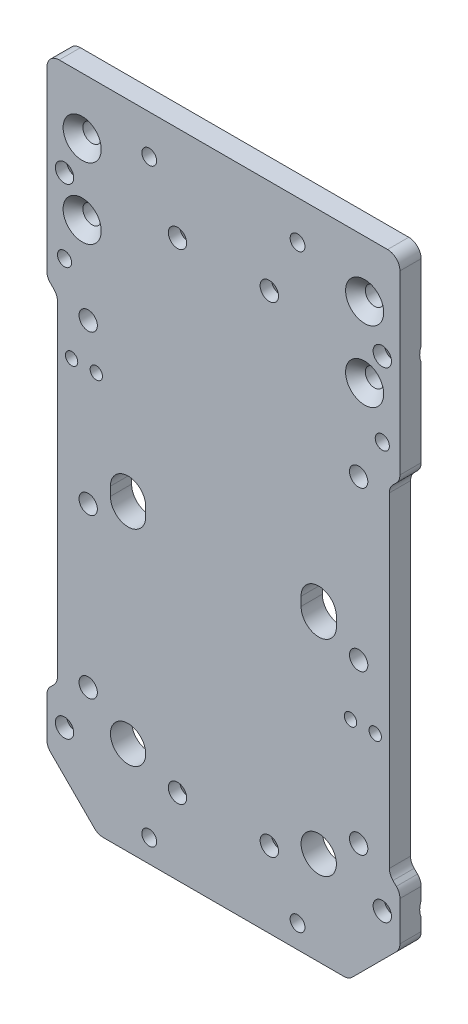
SolidWorks part; units mm, degrees
material "Acrylic (Medium-high impact)"
ref_plane "Front Plane" through (0, 0, 0) normal (0, 0, 1) x (1, 0, 0)
ref_plane "Top Plane" through (0, 0, 0) normal (0, 1, 0) x (1, 0, 0)
ref_plane "Right Plane" through (0, 0, 0) normal (1, 0, 0) x (0, 0, -1)
sketch "Sketch1" plane through (0, 0, 0) normal (0, 0, 1) x (1, 0, 0)
  line L0 (-50, 0) -> (-35.5, -14.5)
  line L1 (-50, 0) -> (50, 0)
  line L2 (-50, 0) -> (-50, 170)
  line L3 (-50, 170) -> (50, 170)
  line L4 (50, 0) -> (50, 170)
  line L5 (-35.5, -14.5) -> (35.5, -14.5)
  line L6 (35.5, -14.5) -> (50, 0)
  point P4 (0, 0)
  point P8 (0, -14.5)
  dimension "D1" = 100
  dimension "D2" = 170
  dimension "D3" = 14.5
  dimension "D4" = 45
extrude "Body" add sketch "Sketch1" along normal mid plane 6 contours L1 L4 L3 L2 | L5 L6 L1 L0 region at (0, -6.8402, 0) region at (0, 85, 0)
sketch "Sketch2" plane through (0, 0, 3) normal (0, 0, 1) x (1, 0, 0)
  line L0 (0, 0) -> (0, 32.3546) construction
  circle A0 centre (-38.3, 20.2) radius 2.6
  circle A1 centre (38.3, 20.2) radius 2.6
  circle A2 centre (-38.3, 110.2) radius 2.6
  circle A3 centre (38.3, 110.2) radius 2.6
  circle A4 centre (-38.3, 65.2) radius 2.6
  circle A5 centre (38.3, 65.2) radius 2.6
  dimension "D1" = 76.6
  dimension "D2" = 5.2
  dimension "D3" = 20.2
  dimension "D4" = 90
  dimension "D5" = 45
extrude "MountToBaseHoles" cut sketch "Sketch2" against normal through all
sketch "Sketch3" plane through (0, 0, 3) normal (0, 0, 1) x (1, 0, 0)
  line L0 (-13, 7) -> (-45, 7) construction
  line L1 (-38.3, 110.2) -> (-77.9825, 110.2) construction
  line L2 (13, 7) -> (13, 37.5378) construction
  line L4 (-13, 7) -> (-13, 44.3761) construction
  line L5 (0, 0) -> (0, 40.72) construction
  circle A0 centre (-45, 7) radius 2.6
  circle A1 centre (-45, 143.1) radius 2.6
  circle A2 centre (45, 143.1) radius 2.6
  circle A3 centre (45, 7) radius 2.6
  circle A6 centre (-13, 143.1) radius 2.6
  circle A7 centre (13, 143.1) radius 2.6
  circle A8 centre (-13, 7) radius 2.6
  circle A9 centre (13, 7) radius 2.6
  dimension "D1" = 5.2
  dimension "D4" = 136.1
  dimension "D6" = 32
  dimension "D2" = 32
  dimension "D3" = 26
  dimension "D7" = 13
  dimension "D5" = 7
extrude "MountRodHoles" cut sketch "Sketch3" against normal through all
sketch "Sketch4" plane through (0, 0, -3) normal (0, 0, -1) x (-1, 0, 0)
  line L1 (0, 0) -> (0, 34.6557) construction
  line L2 (50, 170) -> (-50, 170) construction
  circle A0 centre (-40, 154) radius 2.6
  circle A2 centre (40, 154) radius 2.6
  circle A4 centre (40, 134) radius 2.6
  circle A6 centre (-40, 134) radius 2.6
  dimension "D4" = 5.2
  dimension "D1" = 16
  dimension "D2" = 40
  dimension "D5" = 20
extrude "MountAngleCornerHoles" cut sketch "Sketch4" against normal through all
sketch "Sketch5" plane through (0, 0, -3) normal (0, 0, -1) x (-1, 0, 0)
  circle A0 centre (-21, -8) radius 2.1
  circle A1 centre (21, -8) radius 2.1
  circle A2 centre (-21, 159) radius 2.1
  circle A3 centre (21, 159) radius 2.1
  dimension "D5" = 4.2
  dimension "D1" = 42
  dimension "D2" = 21
  dimension "D3" = 167
  dimension "D4" = 8
extrude "KP8_Holes" cut sketch "Sketch5" against normal through all
chamfer "ChamferForSlottedFlatHeadScrews" distance 2.8 angle 45 14 edges at (-23.1, -8, -3) (-10.4, 7, -3) (15.6, 7, -3) (18.9, -8, -3) (-42.4, 143.1, -3) (-10.4, 143.1, -3) (15.6, 143.1, -3) (47.6, 143.1, -3) (-42.4, 7, -3) (47.6, 7, -3) (-42.6, 154, 3) (-42.6, 134, 3) (37.4, 154, 3) (37.4, 134, 3)
sketch "Sketch6" plane through (0, 0, 3) normal (0, 0, 1) x (1, 0, 0)
  line L0 (-50, 115) -> (-47, 112)
  line L1 (0, 0) -> (0, 25.1631) construction
  line L2 (-47, 112) -> (-47, 17)
  line L3 (-47, 17) -> (-50, 14)
  line L4 (50, 115) -> (47, 112)
  line L6 (47, 112) -> (47, 17)
  line L7 (47, 17) -> (50, 14)
  line L8 (-50, 115) -> (-50, 14)
  line L9 (50, 115) -> (50, 14)
  line L12 (-50, 0) -> (-50, 170) construction
  line L13 (50, 0) -> (50, 170) construction
  dimension "D1" = 3
  dimension "D2" = 3
  dimension "D3" = 45
  dimension "D5" = 115
  dimension "D4" = 14
extrude "ReduceSomeWidth" cut sketch "Sketch6" against normal through all
sketch "screwHeadHoleCarriageY" plane through (0, 0, -3) normal (0, 0, -1) x (-1, 0, 0)
  line L0 (0, 0) -> (0, 34.2129) construction
  line L2 (-27, 70.2) -> (-27, 72.7) construction
  line L3 (-32, 70.2) -> (-32, 72.7)
  line L4 (-22, 70.2) -> (-22, 72.7)
  line L5 (27, 70.2) -> (27, 72.7) construction
  line L6 (22, 70.2) -> (22, 72.7)
  line L7 (32, 70.2) -> (32, 72.7)
  circle A0 centre (-27, 12) radius 5
  circle A1 centre (27, 12) radius 5
  arc A6 (-32, 70.2) -> (-22, 70.2) centre (-27, 70.2) ccw
  arc A7 (-22, 72.7) -> (-32, 72.7) centre (-27, 72.7) ccw
  arc A8 (22, 70.2) -> (32, 70.2) centre (27, 70.2) ccw
  arc A9 (32, 72.7) -> (22, 72.7) centre (27, 72.7) ccw
  point P18 (-27, 71.45)
  point P28 (27, 71.45)
  dimension "D3" = 10
  dimension "D5" = 12.5
  dimension "D1" = 54
  dimension "D2" = 12
  dimension "D4" = 59.45
extrude "CutForOherScrewsHeads" cut sketch "screwHeadHoleCarriageY" against normal through all
sketch "Sketch7" plane through (0, 0, 3) normal (0, 0, 1) x (1, 0, 0)
  line L0 (-35.5, -14.5) -> (35.5, -14.5) construction
  line L2 (50, 0) -> (50, 14) construction
  line L3 (-50, 0) -> (-50, 14) construction
  circle A0 centre (43, 49.5) radius 1.75
  circle A1 centre (36, 49.5) radius 1.75
  circle A2 centre (-36, 98.5) radius 1.75
  circle A3 centre (-43, 98.5) radius 1.75
  dimension "D3" = 3.5
  dimension "D1" = 64
  dimension "D2" = 7
  dimension "D4" = 7
  dimension "D5" = 7
  dimension "D6" = 7
  dimension "D7" = 113
extrude "EndSensorsHoles" cut sketch "Sketch7" against normal through all
chamfer "ChamferEndSensors" distance 1.5 angle 45 4 edges at (37.75, 49.5, -3) (44.75, 49.5, -3) (-41.25, 98.5, -3) (-34.25, 98.5, -3)
sketch "Sketch8" plane through (0, 0, 3) normal (0, 0, 1) x (1, 0, 0)
  line L0 (0, 0) -> (0, 36.091) construction
  circle A0 centre (45, 122) radius 2
  circle A1 centre (-45, 122) radius 2
  dimension "D1" = 4
  dimension "D2" = 90
  dimension "D3" = 122
extrude "CableTieHoles" cut sketch "Sketch8" against normal through all
fillet "EndMillMinimumRadius" radius 3.5 14 edges at (-50, 170, 0) (50, 170, 0) (47, 112, 0) (47, 17, 0) (-47, 17, 0) (-47, 112, 0) (-50, 14, 0) (-50, 0, 0) (-35.5, -14.5, 0) (50, 14, 0) (50, 0, 0) (35.5, -14.5, 0) (-50, 115, 0) (50, 115, 0)
equation "\"D6@Sketch3\"=\"D2@Sketch3\""
equation "\"D7@Sketch3\"=\"D3@Sketch3\"/2"
equation "\"D1@Sketch6\"=\"D2@Sketch6\""
